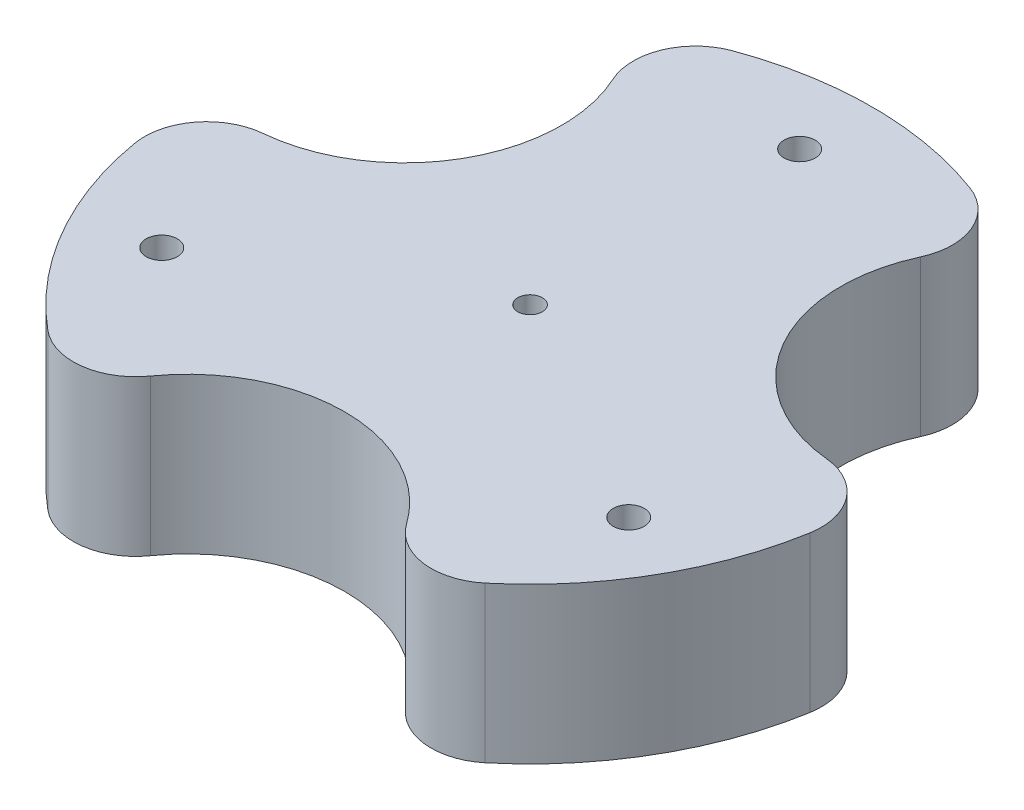
SolidWorks part; units mm, degrees
ref_plane "Front Plane" through (0, 0, 0) normal (0, 0, 1) x (1, 0, 0)
ref_plane "Top Plane" through (0, 0, 0) normal (0, 1, 0) x (1, 0, 0)
ref_plane "Right Plane" through (0, 0, 0) normal (1, 0, 0) x (0, 0, -1)
sketch "Sketch1" plane through (0, 0, 0) normal (0, 1, 0) x (1, 0, 0)
  circle A0 centre (0, 0) radius 13.97
  dimension "D1" = 27.94
extrude "Boss-Extrude1" add sketch "Sketch1" along normal blind 6.35
sketch "Sketch2" plane through (0, 6.35, 0) normal (0, 1, 0) x (1, 0, 0)
  line L0 (0, -11) -> (0, 11) construction
  circle A0 centre (0, 11) radius 0.635
  dimension "D1" = 22
  dimension "D2" = 1.27
extrude "Cut-Extrude1" cut sketch "Sketch2" against normal through all
ref_axis "Axis1" through (0, 6.35, 0) along (0, -1, 0)
pattern_circular "CirPattern1" count 3 over 360 about axis through (0, 6.35, 0) along (0, -1, 0) of "Cut-Extrude1"
sketch "Sketch3" plane through (0, 6.35, 0) normal (0, 1, 0) x (1, 0, 0)
  circle A0 centre (0, 0) radius 1.143
  dimension "D1" = 2.286
sketch "Sketch4" plane through (0, 6.35, 0) normal (0, 1, 0) x (1, 0, 0)
  line L0 (0, 0) -> (0, -13.97) construction
  circle A0 centre (0, -13.97) radius 6.4068
  circle A1 centre (0, 0) radius 13.97 construction
extrude "Cut-Extrude3" cut sketch "Sketch4" against normal through all
pattern_circular "CirPattern2" count 3 over 360 about axis through (0, 6.35, 0) along (0, -1, 0) of "Cut-Extrude3"
fillet "Fillet1" radius 2.54 6 edges at (13.9441, 3.175, -0.8498) (6.2361, 3.175, 12.5009) (-6.2361, 3.175, 12.5009) (-13.9441, 3.175, -0.8498) (-7.708, 3.175, -11.6511) (7.708, 3.175, -11.6511)
hole_wizard "Ø1.0mm Press Dowel Hole1" positions "Sketch8" profile "Sketch5" hole size "Ø1.0" standard "ANSI Metric"
sketch "Sketch8" plane through (0, 6.35, 0) normal (0, 1, 0) x (1, 0, 0)
  point P0 (0, 0)
sketch "Sketch5" plane through (0, 6.35, 0) normal (1, 0, 0) x (0, 0, 1)
  line L0 (0, 0) -> (0, 25.1924)
  line L1 (0, 25.1924) -> (0.5, 24.892)
  line L2 (0.5, 24.892) -> (0.5, 0)
  line L5 (0.5, 0) -> (0, 0)
  line L10 (0, 25.1924) -> (-0.5, 24.892) construction
  line L11 (0, -6.35) -> (0, 107.95) construction
  dimension "Hole Dia." = 1
  dimension "Hole Depth" = 24.892
  dimension "Drill Angle" = 118
